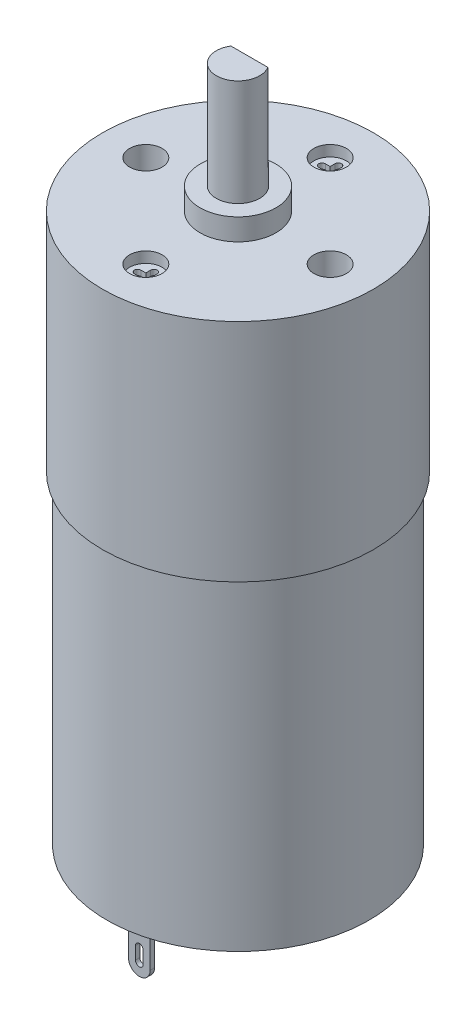
SolidWorks part; units mm, degrees
ref_plane "Plano frontal" through (0, 0, 0) normal (0, 0, 1) x (1, 0, 0)
ref_plane "Plano superior" through (0, 0, 0) normal (0, 1, 0) x (1, 0, 0)
ref_plane "Plano direito" through (0, 0, 0) normal (1, 0, 0) x (0, 0, -1)
sketch "Esboço1" plane through (0, 0, 0) normal (0, 1, 0) x (1, 0, 0)
  circle A0 centre (0, 0) radius 12.5
  dimension "D1" = 25
extrude "Ressalto-extrusão1" add sketch "Esboço1" along normal blind 20.8
sketch "Esboço2" plane through (0, 0, 0) normal (0, -1, 0) x (-1, 0, 0)
  circle A0 centre (0, 0) radius 12.1
  dimension "D1" = 24.2
extrude "Ressalto-extrusão2" add sketch "Esboço2" along normal blind 29.8
sketch "Esboço3" plane through (0, 20.8, 0) normal (0, 1, 0) x (1, 0, 0)
  circle A0 centre (0, 0) radius 2
  dimension "D1" = 4
extrude "Ressalto-extrusão3" add sketch "Esboço3" along normal blind 11.8
sketch "Esboço4" plane through (0, 32.6, 0) normal (0, 1, 0) x (1, 0, 0)
  line L0 (-1.7027, 1.0493) -> (1.7027, 1.0493)
  circle A0 centre (0, 0) radius 2 construction
  circle A1 centre (0, 0) radius 2 construction
  arc A2 (1.7027, 1.0493) -> (-1.7027, 1.0493) centre (0, 0) ccw
extrude "Corte-extrusão1" cut sketch "Esboço4" against normal blind 8.1
sketch "Esboço5" plane through (0, 20.8, 0) normal (0, 1, 0) x (1, 0, 0)
  circle A0 centre (0, 0) radius 3.5
  dimension "D1" = 7
extrude "Ressalto-extrusão4" add sketch "Esboço5" along normal blind 2
sketch "Esboço6" plane through (0, 20.8, 0) normal (0, 1, 0) x (1, 0, 0)
  circle A0 centre (0, 8.5) radius 1.5
  circle A1 centre (8.5, 0) radius 1.5
  circle A2 centre (0, -8.5) radius 1.5
  circle A3 centre (-8.5, 0) radius 1.5
  point P12 (0, 0)
  dimension "D2" = 3
  dimension "D4" = 3
  dimension "D1" = 8.5
  dimension "D3" = 4
extrude "Corte-extrusão2" cut sketch "Esboço6" against normal blind 10
sketch "Esboço8" plane through (0, 10.8, 0) normal (0, 1, 0) x (1, 0, 0)
  circle A0 centre (0, 8.5) radius 1.5
  circle A1 centre (0, -8.5) radius 1.5
extrude "Ressalto-extrusão5" add sketch "Esboço8" along normal blind 9
sketch "Esboço9" plane through (0, 19.8, 0) normal (0, 1, 0) x (1, 0, 0)
  line L0 (-0.3, 8.2) -> (-0.3, 7.75)
  line L1 (0.3, 9.25) -> (0.3, 8.8)
  line L2 (-0.3, 9.25) -> (-0.3, 8.8)
  line L3 (0.3, -8.2) -> (0.3, -7.75)
  line L4 (-0.75, 8.8) -> (-0.3, 8.8)
  line L5 (-0.75, 8.2) -> (-0.3, 8.2)
  line L6 (0.3, 8.2) -> (0.75, 8.2)
  line L7 (0.3, 8.2) -> (0.3, 7.75)
  line L8 (0.3, 8.8) -> (0.75, 8.8)
  line L9 (-0.3, -9.25) -> (-0.3, -8.8)
  line L10 (0.3, -9.25) -> (0.3, -8.8)
  line L11 (0.75, -8.8) -> (0.3, -8.8)
  line L12 (0.75, -8.2) -> (0.3, -8.2)
  line L13 (-0.3, -8.2) -> (-0.75, -8.2)
  line L14 (-0.3, -8.2) -> (-0.3, -7.75)
  line L15 (-0.3, -8.8) -> (-0.75, -8.8)
  arc A0 (0.3, 9.25) -> (-0.3, 9.25) centre (0, 9.25) ccw
  arc A1 (-0.3, 7.75) -> (0.3, 7.75) centre (0, 7.75) ccw
  arc A2 (-0.75, 8.8) -> (-0.75, 8.2) centre (-0.75, 8.5) ccw
  arc A3 (0.75, 8.2) -> (0.75, 8.8) centre (0.75, 8.5) ccw
  arc A4 (-0.3, -9.25) -> (0.3, -9.25) centre (0, -9.25) ccw
  arc A5 (0.3, -7.75) -> (-0.3, -7.75) centre (0, -7.75) ccw
  arc A6 (0.75, -8.8) -> (0.75, -8.2) centre (0.75, -8.5) ccw
  arc A7 (-0.75, -8.2) -> (-0.75, -8.8) centre (-0.75, -8.5) ccw
  point P2 (0, 8.5)
  point P11 (0, 8.5)
  point P25 (0, -8.5)
  point P32 (0, -8.5)
  point P41 (0, 0)
  dimension "D2" = 0.3
  dimension "D3" = 0.3
  dimension "D1" = 1.5
  dimension "D4" = 1.5
  dimension "D5" = 2
extrude "Corte-extrusão3" cut sketch "Esboço9" against normal blind 0.5
sketch "Esboço10" plane through (0, -29.8, 0) normal (0, -1, 0) x (1, 0, 0)
  circle A0 centre (0, 0) radius 4.25
  dimension "D1" = 8.5
extrude "Ressalto-extrusão6" add sketch "Esboço10" along normal blind 2.8
sketch "Esboço11" plane through (0, -29.8, 0) normal (0, -1, 0) x (-1, 0, 0)
  line L0 (-1, 9.1) -> (1, 9.1)
  line L1 (1, -9.1) -> (-1, -9.1)
  line L2 (1, -9.1) -> (1, -8.7)
  line L3 (1, -8.7) -> (-1, -8.7)
  line L4 (-1, -9.1) -> (-1, -8.7)
  line L5 (1, -9.1) -> (-1, -8.7) construction
  line L6 (1, -8.7) -> (-1, -9.1) construction
  line L7 (-1, 9.1) -> (-1, 8.7)
  line L8 (-1, 8.7) -> (1, 8.7)
  line L9 (1, 9.1) -> (1, 8.7)
  line L10 (-1, 9.1) -> (1, 8.7) construction
  point P0 (0, -8.9)
  point P8 (0, 8.9)
  point P13 (0, 0)
  dimension "D1" = 8.9
  dimension "D2" = 2
  dimension "D3" = 0.4
  dimension "D4" = 2
extrude "Ressalto-extrusão8" add sketch "Esboço11" along normal blind 6
fillet "Filete1" radius 1 4 edges at (1, -35.8, -8.9) (-1, -35.8, -8.9) (-1, -35.8, 8.9) (1, -35.8, 8.9)
sketch "Esboço12" plane through (0, 0, 9.1) normal (0, 0, 1) x (1, 0, 0)
  line L0 (0, -33.5108) -> (0, -34.6689) construction
  line L1 (0.3558, -33.5108) -> (0.3558, -34.6689)
  line L2 (-0.3558, -33.5108) -> (-0.3558, -34.6689)
  arc A0 (0.3558, -33.5108) -> (-0.3558, -33.5108) centre (0, -33.5108) ccw
  arc A1 (-0.3558, -34.6689) -> (0.3558, -34.6689) centre (0, -34.6689) ccw
  point P2 (0, -34.0898)
extrude "Corte-extrusão4" cut sketch "Esboço12" against normal blind 22
